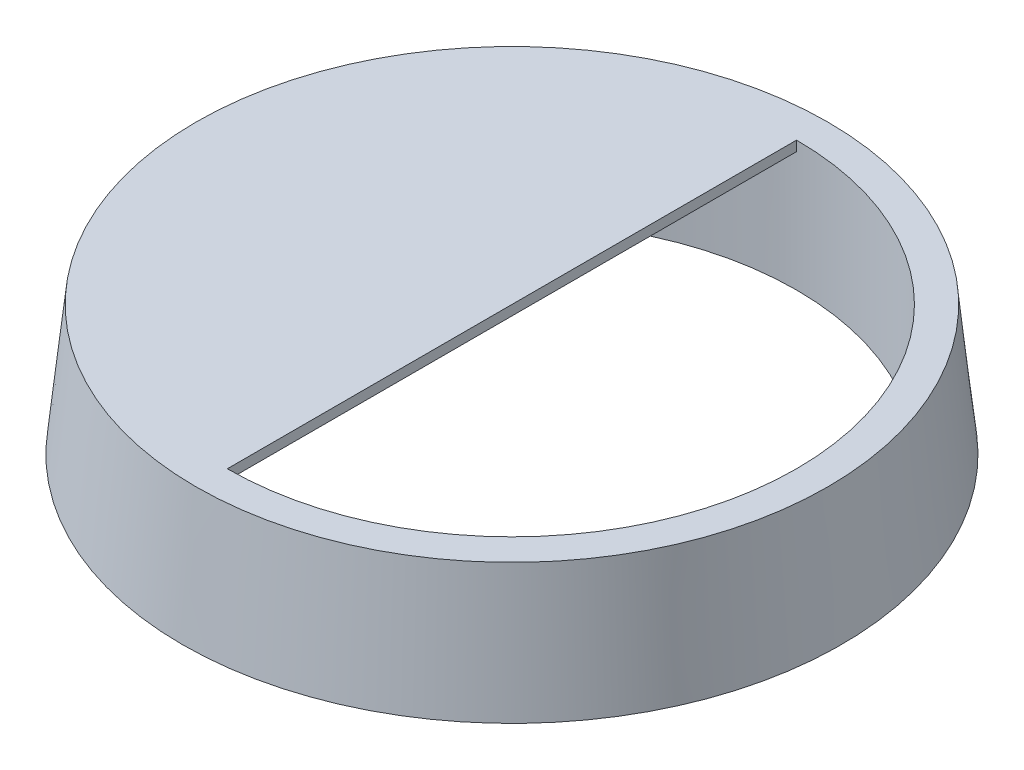
SolidWorks part; units mm, degrees
ref_plane "Front Plane" through (0, 0, 0) normal (0, 0, 1) x (1, 0, 0)
ref_plane "Top Plane" through (0, 0, 0) normal (0, 1, 0) x (1, 0, 0)
ref_plane "Right Plane" through (0, 0, 0) normal (1, 0, 0) x (0, 0, -1)
sketch "Sketch1" plane through (0, 0, 0) normal (0, 1, 0) x (1, 0, 0)
  circle A0 centre (0, 0) radius 16.5
  dimension "D1" = 33
extrude "Boss-Extrude1" add sketch "Sketch1" along normal blind 6.5 draft 6
sketch "Sketch2" plane through (0, 0, 0) normal (0, -1, 0) x (1, 0, 0)
  circle A0 centre (0, 0) radius 14.25
  dimension "D1" = 28.5
extrude "Cut-Extrude1" cut sketch "Sketch2" against normal blind 4.5
sketch "Sketch3" plane through (0, 6.5, 0) normal (0, 1, 0) x (1, 0, 0)
  line L0 (0, -14.25) -> (0, 14.25)
  arc A0 (0, -14.25) -> (0, 14.25) centre (0, 0) ccw
  dimension "D1" = 28.5
extrude "Cut-Extrude2" cut sketch "Sketch3" against normal blind 6
chamfer "Chamfer1" distance 1.5 angle 45 1 edges at (0, 4.5, 0)
